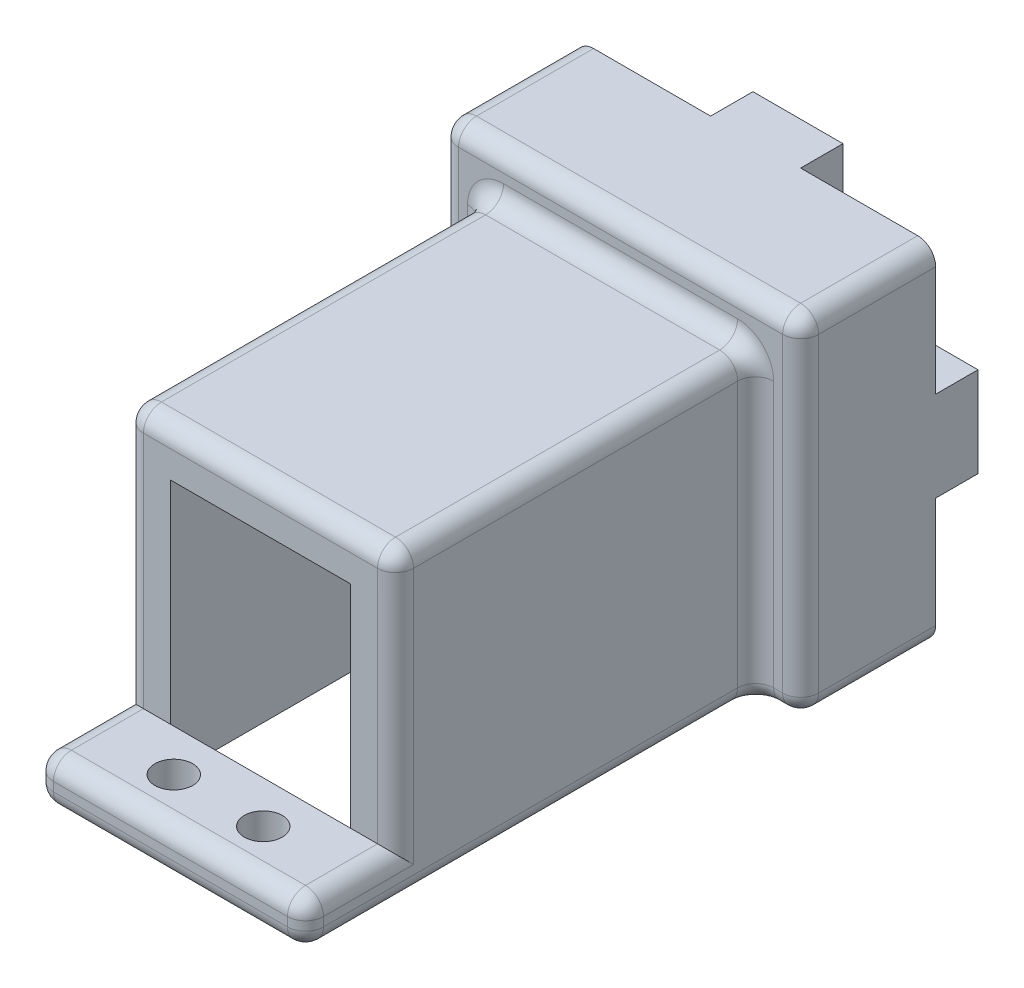
SolidWorks part; units mm, degrees
material "ABS"
ref_plane "Front Plane" through (0, 0, 0) normal (0, 0, 1) x (1, 0, 0)
ref_plane "Top Plane" through (0, 0, 0) normal (0, 1, 0) x (1, 0, 0)
ref_plane "Right Plane" through (0, 0, 0) normal (1, 0, 0) x (0, 0, -1)
sketch "Sketch1" plane through (0, 0, 0) normal (0, 0, 1) x (1, 0, 0)
  line L1 (-20, -19.25) -> (20, -19.25)
  line L2 (-20, -19.25) -> (-20, 19.25)
  line L3 (-20, 19.25) -> (20, 19.25)
  line L4 (20, -19.25) -> (20, 19.25)
  line L5 (-20, -19.25) -> (20, 19.25) construction
  line L6 (-20, 19.25) -> (20, -19.25) construction
  line L8 (-15, -19.25) -> (15, -19.25)
  line L9 (-15, -19.25) -> (-15, 14.25)
  line L10 (-15, 14.25) -> (15, 14.25)
  line L11 (15, -19.25) -> (15, 14.25)
  line L12 (10, -14.25) -> (10, 9.25)
  line L13 (-10, 9.25) -> (10, 9.25)
  line L14 (-10, -14.25) -> (-10, 9.25)
  line L15 (-10, -14.25) -> (10, -14.25)
  point P0 (0, 0)
  dimension "D1" = 40
  dimension "D2" = 38.5
  dimension "D5" = 5
  dimension "D3" = 5
  dimension "D4" = 5
  dimension "D7" = 20
  dimension "D8" = 23.5
  dimension "D6" = 5
extrude "Boss-Extrude1" add sketch "Sketch1" against normal blind 10 contours L11 L1 L4 L3 L2 L9 L10 | L1 L11 L10 L9 L15 L14 L13 L12 | L14 L15 L12 L13 region at (-19.4448, 0, 0) region at (-14.5503, -2.5, 0) region at (0, -2.5, 0)
extrude "Boss-Extrude2" add sketch "Sketch1<4>" along normal blind 5 contours L1 L11 L10 L9 L15 L14 L13 L12 region at (-14.5503, -2.5, 0)
sketch "Sketch1<4>" plane through (0, 0, 0) normal (0, 0, 1) x (1, 0, 0) same geometry as "Sketch1"
sketch "Sketch2" plane through (0, 0, 5) normal (0, 0, 1) x (1, 0, 0)
  line L1 (-20, -19.25) -> (20, -19.25)
  line L2 (-20, -19.25) -> (-20, 19.25)
  line L3 (-20, 19.25) -> (20, 19.25)
  line L4 (20, -19.25) -> (20, 19.25)
  line L5 (-20, -19.25) -> (20, 19.25) construction
  line L6 (-20, 19.25) -> (20, -19.25) construction
  point P0 (0, 0)
extrude "Boss-Extrude3" add sketch "Sketch2" against normal blind 10
sketch "Sketch3" plane through (0, 0, 5) normal (0, 0, 1) x (1, 0, 0)
  line L0 (-10, -14.25) -> (-10, -19.25)
  line L1 (10, -14.25) -> (10, -19.25)
  line L4 (10, -14.25) -> (10, 9.25)
  line L5 (10, 9.25) -> (-10, 9.25)
  line L6 (-10, 9.25) -> (-10, -14.25)
  line L7 (-10, -14.25) -> (10, -14.25)
  line L8 (10, -14.25) -> (10, 9.25)
  line L9 (10, 9.25) -> (-10, 9.25)
  line L10 (-10, 9.25) -> (-10, -14.25)
  line L12 (-15, -19.25) -> (15, -19.25)
  line L13 (15, -19.25) -> (15, 14.25)
  line L14 (15, 14.25) -> (-15, 14.25)
  line L15 (-15, 14.25) -> (-15, -19.25)
  line L16 (-15, -19.25) -> (15, -19.25)
  line L17 (15, -19.25) -> (15, 14.25)
  line L18 (15, 14.25) -> (-15, 14.25)
  line L19 (-15, 14.25) -> (-15, -19.25)
  line M13 (-20, -19.25) -> (20, -19.25)
  dimension "D1" = 0
  dimension "D2" = 0
extrude "Boss-Extrude4" add sketch "Sketch3" along normal blind 40 contours L18 L19 L0 L10 L9 L8 L1 L17 M13 region at (-10.4497, -16.75, 5)
sketch "Sketch4" plane through (0, 0, 45) normal (0, 0, 1) x (1, 0, 0)
  line L0 (-15, -14.25) -> (15, -14.25)
  line L1 (-15, 14.25) -> (-15, -19.25) construction
  line L2 (15, -19.25) -> (15, 14.25) construction
  line L3 (15, -14.25) -> (15, -19.25)
  line L4 (15, -19.25) -> (-15, -19.25)
  line L5 (-15, -19.25) -> (-15, -14.25)
  dimension "D1" = 5
extrude "Boss-Extrude5" add sketch "Sketch4" along normal blind 10
sketch "Sketch5" plane through (0, -19.25, 0) normal (0, -1, 0) x (1, 0, 0)
  line L0 (15, 55) -> (15, 5) construction
  line L1 (-15, 55) -> (-15, 5) construction
  line L2 (-10, 45) -> (10, 45) construction
  circle A0 centre (4.97, 49.66) radius 2.1
  circle A1 centre (-4.97, 49.66) radius 2.1
  dimension "D3" = 4.2
  dimension "D1" = 10.03
  dimension "D2" = 10.03
  dimension "D4" = 4.66
extrude "Cut-Extrude1" cut sketch "Sketch5" against normal up to surface (5 mm away) up to face at (0, -14.25, 48.3333)
fillet "Fillet1" radius 2 25 edges at (17.5, -19.25, 5) (-17.5, -19.25, 5) (15, -19.25, 30) (15, -16.75, 55) (15, -14.25, 50) (15, 0, 45) (15, -2.5, 5) (-15, 0, 45) (-15, -14.25, 50) (-15, -16.75, 55) (-15, -19.25, 30) (-15, -2.5, 5) (15, 14.25, 25) (0, 14.25, 45) (-15, 14.25, 25) (0, 14.25, 5) (-20, -19.25, -2.5) (-20, 0, 5) (-20, 19.25, -2.5) (0, 19.25, 5) (20, 19.25, -2.5) (20, -19.25, -2.5) (20, 0, 5) (0, -19.25, 55) (0, -14.25, 55)
sketch "Sketch6" plane through (0, 0, -10) normal (0, 0, -1) x (-1, 0, 0)
  line L1 (-5, -19.25) -> (5, -19.25)
  line L2 (-5, -19.25) -> (-5, -14.25)
  line L3 (-5, -14.25) -> (5, -14.25)
  line L4 (5, -19.25) -> (5, -14.25)
  line L5 (-5, -19.25) -> (5, -14.25) construction
  line L6 (-5, -14.25) -> (5, -19.25) construction
  line L7 (20, -5) -> (15, -5)
  line L8 (20, -5) -> (20, 5)
  line L9 (20, 5) -> (15, 5)
  line L10 (15, -5) -> (15, 5)
  line L11 (20, -5) -> (15, 5) construction
  line L12 (20, 5) -> (15, -5) construction
  line L13 (-5, 19.25) -> (5, 19.25)
  line L14 (-5, 19.25) -> (-5, 14.25)
  line L15 (-5, 14.25) -> (5, 14.25)
  line L16 (5, 19.25) -> (5, 14.25)
  line L17 (-5, 19.25) -> (5, 14.25) construction
  line L18 (-5, 14.25) -> (5, 19.25) construction
  line L19 (-20, -5) -> (-15, -5)
  line L20 (-20, -5) -> (-20, 5)
  line L21 (-20, 5) -> (-15, 5)
  line L22 (-15, -5) -> (-15, 5)
  line L23 (-20, -5) -> (-15, 5) construction
  line L24 (-20, 5) -> (-15, -5) construction
  line L28 (20, -17.25) -> (20, 17.25) construction
  line L29 (-20, -17.25) -> (-20, 17.25) construction
  line L30 (18, 19.25) -> (-18, 19.25) construction
  line L31 (18, -19.25) -> (-18, -19.25) construction
  point P0 (0, -16.75)
  point P5 (17.5, 0)
  point P10 (0, 16.75)
  point P15 (-17.5, 0)
  dimension "D1" = 10
  dimension "D2" = 10
  dimension "D3" = 10
  dimension "D4" = 10
  dimension "D5" = 5
  dimension "D6" = 5
  dimension "D7" = 5
  dimension "D8" = 5
extrude "Boss-Extrude6" add sketch "Sketch6" along normal blind 4.7
sketch "Sketch7" plane through (0, 0, 5) normal (0, 0, 1) x (1, 0, 0)
  line L0 (-10, 9.25) -> (-10, -5.75)
  line L1 (-10, 9.25) -> (10, 9.25)
  line L2 (-10, 9.25) -> (-10, -19.25) construction
  line L3 (-10, -5.75) -> (10, -5.75)
  line L4 (10, -14.25) -> (10, 9.25) construction
  line L5 (10, -5.75) -> (10, 9.25)
  dimension "D1" = 15
extrude "Cut-Extrude2" cut sketch "Sketch7" against normal up to surface (15 mm away) up to face at (0, 0, -10)
